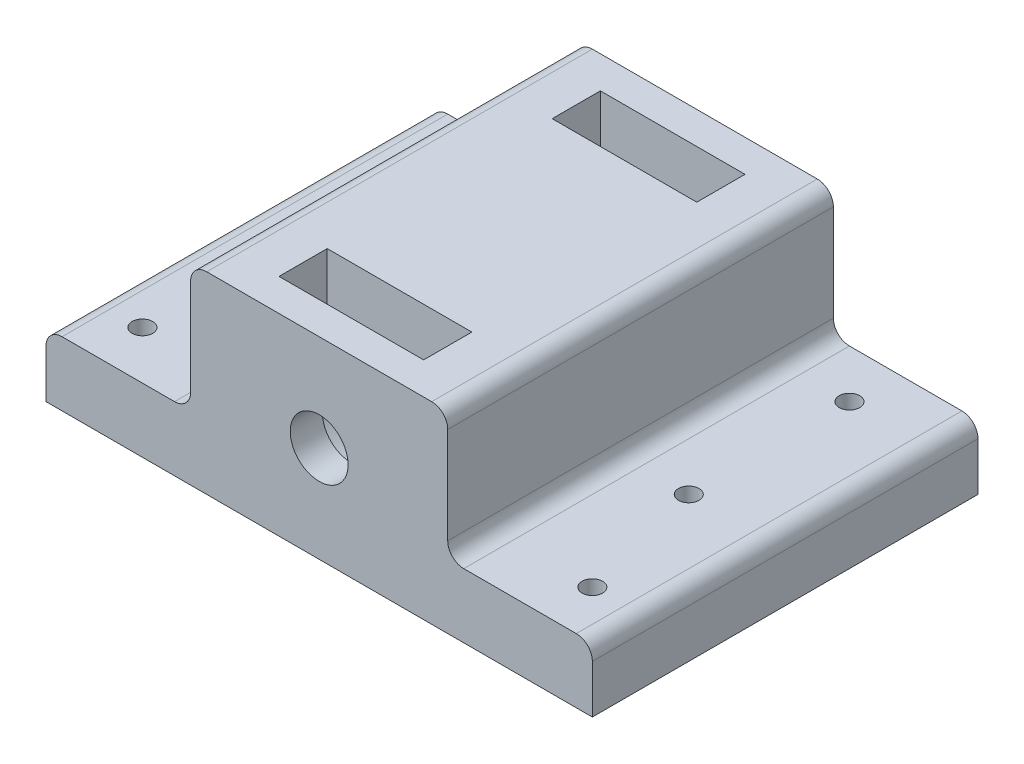
SolidWorks part; units mm, degrees
ref_plane "Front Plane" through (0, 0, 0) normal (0, 0, 1) x (1, 0, 0)
ref_plane "Top Plane" through (0, 0, 0) normal (0, 1, 0) x (1, 0, 0)
ref_plane "Right Plane" through (0, 0, 0) normal (1, 0, 0) x (0, 0, -1)
sketch "Sketch2" plane through (0, 0, 0) normal (0, 0, 1) x (1, 0, 0)
  line L0 (0, 30) -> (85, 0) construction
  line L1 (0, 0) -> (85, 0)
  line L2 (0, 0) -> (0, 30)
  line L3 (0, 30) -> (85, 30)
  line L4 (85, 0) -> (85, 30)
  line L5 (42.5, 30) -> (42.5, 15) construction
  line L6 (62.5, 30) -> (85, 30)
  line L7 (62.5, 30) -> (62.5, 10)
  line L8 (62.5, 10) -> (85, 10)
  line L9 (85, 30) -> (85, 10)
  line L10 (22.5, 10) -> (0, 10)
  line L11 (22.5, 30) -> (22.5, 10)
  circle A0 centre (42.5, 15) radius 4.5
  dimension "D3" = 9
  dimension "D1" = 30
  dimension "D2" = 85
  dimension "D4" = 20
  dimension "D5" = 22.5
extrude "Boss-Extrude1" add sketch "Sketch2" along normal blind 15 and the other way blind 45 contours L3 L11 L10 L2 L1 L4 L8 L7 A0 region at (0.9014, 5, 0)
sketch "Sketch3" plane through (0, 0, 0) normal (0, 1, 0) x (1, 0, 0)
  line L0 (0, -7.5) -> (85, -7.5) construction
  line L2 (22.5, 45) -> (62.5, 45) construction
  line L3 (42.5, 45) -> (42.5, -15) construction
  line L10 (0, 45) -> (0, -15) construction
  line L11 (85, 45) -> (85, -15) construction
  line L12 (22.5, -15) -> (62.5, -15) construction
  circle A0 centre (7.5, -7.5) radius 1.6
  circle A1 centre (77.5, -7.5) radius 1.6
  circle A2 centre (72.5, 12.5) radius 1.6
  circle A3 centre (12.5, 12.5) radius 1.6
  circle A4 centre (72.5, 37.5) radius 1.6
  circle A5 centre (12.5, 37.5) radius 1.6
  point P15 (0, 0)
  point P19 (0, 0)
  point P21 (0, 0)
  point P22 (42.5, 45)
  dimension "D1" = 3.2
  dimension "D3" = 3.2
  dimension "D4" = 20
  dimension "D6" = 7.5
  dimension "D7" = 25
  dimension "D2" = 70
  dimension "D5" = 30
extrude "Cut-Extrude1" cut sketch "Sketch3" along normal through all both and the other way through all contours A2 | A3 | A0 | A1 | A5 | A4 region at (7.5, 0, 7.5) region at (77.5, 0, 7.5) region at (72.5, 0, -12.5) region at (12.5, 0, -12.5) region at (72.5, 0, -37.5) region at (12.5, 0, -37.5)
fillet "Fillet1" radius 2.5 6 edges at (62.5, 10, -15) (22.5, 10, -15) (85, 10, -15) (0, 10, -15) (62.5, 30, -15) (22.5, 30, -15)
ref_plane "Plane1" through (0, 0, 10) normal (0, 0, 1) x (1, 0, 0)
sketch "Sketch5" plane through (0, 0, 0) normal (0, 0, 1) x (1, 0, 0)
  line L0 (42.5, 15) -> (42.5, 30) construction
  line L1 (25, 30) -> (60, 30) construction
  line L3 (31.25, 30) -> (31.25, 15.25)
  line L4 (31.25, 15.25) -> (53.75, 15.25) construction
  line L5 (53.75, 15.25) -> (53.75, 30)
  line L6 (53.75, 30) -> (31.25, 30)
  arc A0 (53.75, 15.25) -> (31.25, 15.25) centre (42.5, 15.25) cw
  circle A1 centre (42.5, 15) radius 4.5 construction
  circle A2 centre (42.5, 15) radius 4.5 construction
  point P5 (42.5, 4)
  point P12 (42.5, 15)
  dimension "D1" = 11
  dimension "D2" = 22.5
extrude "Cut-Extrude5" cut sketch "Sketch5" against normal blind 7.5 from surface starting at plane "Plane1"
ref_plane "Plane2" through (0, 0, -40) normal (0, 0, -1) x (-1, 0, 0)
extrude "Cut-Extrude6" cut sketch "Sketch5<2>" along normal blind 7.5 from surface starting at plane "Plane2"
sketch "Sketch5<2>" plane through (0, 0, 0) normal (0, 0, 1) x (1, 0, 0) same geometry as "Sketch5"
